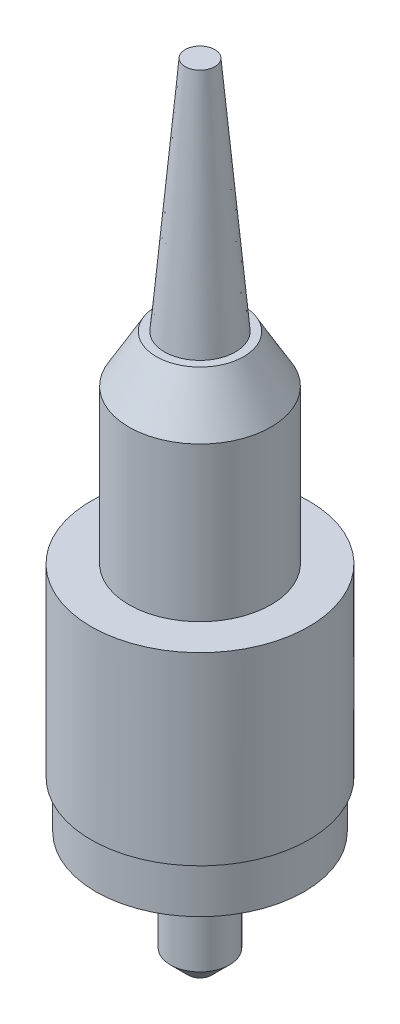
SolidWorks part; units mm, degrees
material "铸造合金钢"
ref_plane "前视基准面" through (0, 0, 0) normal (0, 0, 1) x (1, 0, 0)
ref_plane "上视基准面" through (0, 0, 0) normal (0, 1, 0) x (1, 0, 0)
ref_plane "右视基准面" through (0, 0, 0) normal (1, 0, 0) x (0, 0, -1)
sketch "草图1" plane through (0, 0, 0) normal (0, 1, 0) x (1, 0, 0)
  circle A0 centre (0, 0) radius 4.6
  dimension "D1" = 9.2
extrude "拉伸1" add sketch "草图1" along normal blind 9.8
sketch "草图2" plane through (0, 0, 0) normal (0, -1, 0) x (1, 0, 0)
  circle A0 centre (0, 0) radius 4.6 construction
  circle A1 centre (0, 0) radius 4.4
  circle A2 centre (0, 0) radius 4.6
  dimension "D1" = 0.2
extrude "切除-拉伸1" cut sketch "草图2" against normal blind 2
sketch "草图3" plane through (0, 0, 0) normal (0, -1, 0) x (1, 0, 0)
  circle A0 centre (0, 0) radius 3.9
  circle A1 centre (0, 0) radius 2.9
  dimension "D1" = 5.8
  dimension "D2" = 1
extrude "切除-拉伸2" cut sketch "草图3" against normal blind 4
sketch "草图4" plane through (0, 0, 0) normal (0, -1, 0) x (1, 0, 0)
  circle A1 centre (0, 0) radius 2.4
  dimension "D1" = 4.8
extrude "切除-拉伸3" cut sketch "草图4" against normal blind 5
sketch "草图5" plane through (0, 5, 0) normal (0, -1, 0) x (1, 0, 0)
  circle A0 centre (0, 0) radius 1.25
  dimension "D1" = 2.5
extrude "拉伸4" add sketch "草图5" along normal blind 10
chamfer "倒角1" distance 0.75 angle 45 1 edges at (0, -5, -1.25)
sketch "草图6" plane through (0, 0, 0) normal (0, -1, 0) x (1, 0, 0)
  circle A0 centre (0, 0) radius 2.4 construction
  circle A1 centre (0, 0) radius 2.9 construction
  circle A2 centre (0, 0) radius 2.4
  circle A3 centre (0, 0) radius 2.9
extrude "拉伸5" add sketch "草图6" along normal blind 1
sketch "草图7" plane through (0, 9.8, 0) normal (0, 1, 0) x (-1, 0, 0)
  circle A0 centre (0, 0) radius 3
  dimension "D1" = 6
extrude "拉伸6" add sketch "草图7" along normal blind 8.5
chamfer "倒角2" distance 2 angle 30 1 edges at (0, 18.3, 3) first distance on face at (0, 18.3, 3)
sketch "草图8" plane through (0, 18.3, 0) normal (0, 1, 0) x (-1, 0, 0)
  circle A0 centre (0, 0) radius 1.5
  dimension "D1" = 3
extrude "拉伸7" add sketch "草图8" along normal blind 10
chamfer "倒角3" distance 10 angle 5 1 edges at (0, 28.3, 1.5) first distance on face at (0, 28.3, 1.5)
